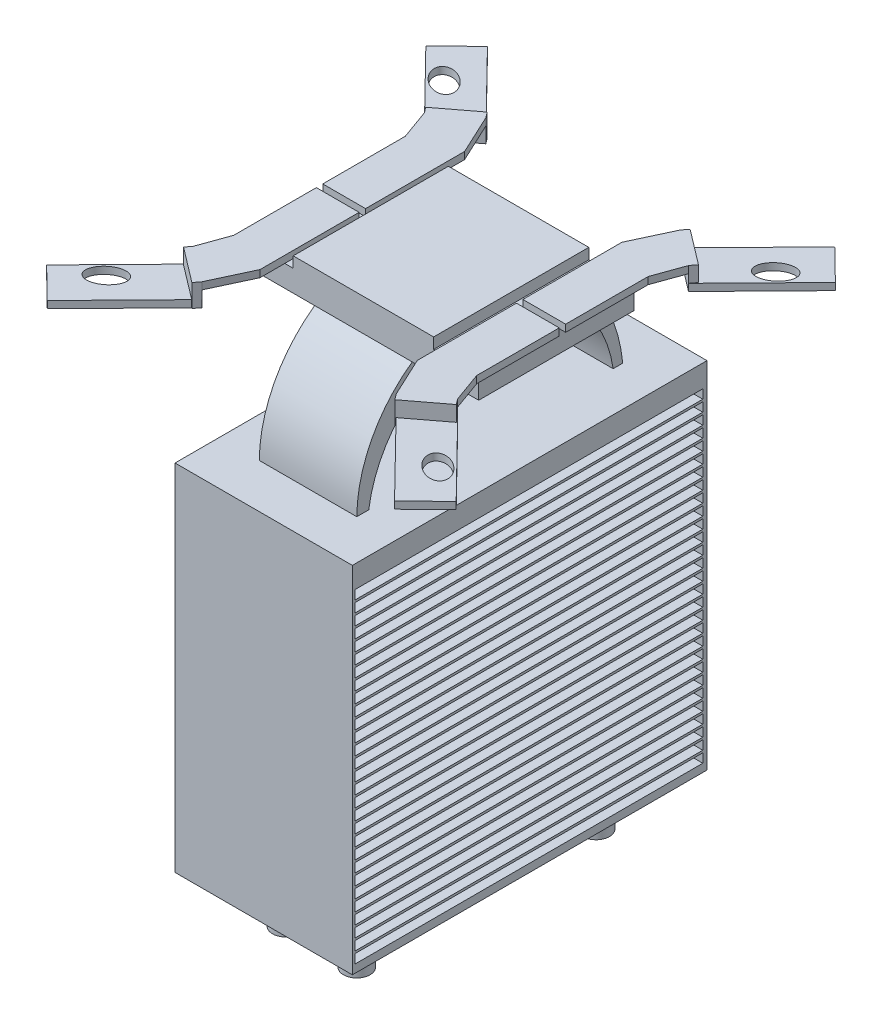
SolidWorks part; units mm, degrees
ref_plane "Front Plane" through (0, 0, 0) normal (0, 0, 1) x (1, 0, 0)
ref_plane "Top Plane" through (0, 0, 0) normal (0, 1, 0) x (1, 0, 0)
ref_plane "Right Plane" through (0, 0, 0) normal (1, 0, 0) x (0, 0, -1)
sketch "Sketch1" plane through (0, 0, 0) normal (0, 1, 0) x (1, 0, 0)
  line L1 (-52.1271, 39.0529) -> (-12.1271, 39.0529)
  line L2 (-52.1271, 39.0529) -> (-52.1271, -40.9471)
  line L3 (-52.1271, -40.9471) -> (-12.1271, -40.9471)
  line L4 (-12.1271, 39.0529) -> (-12.1271, -40.9471)
  dimension "D1" = 40
  dimension "D2" = 80
extrude "Boss-Extrude1" add sketch "Sketch1" along normal blind 80
sketch "Sketch2" plane through (0, 0, 0) normal (0, -1, 0) x (1, 0, 0)
  line L0 (-52.1271, -39.0529) -> (-52.1271, 40.9471) construction
  line L1 (-12.1271, 40.9471) -> (-12.1271, -39.0529) construction
  line L2 (-52.1271, 40.9471) -> (-12.1271, 40.9471) construction
  line L3 (-12.1271, -39.0529) -> (-52.1271, -39.0529) construction
  circle A0 centre (-40.1271, 27.9471) radius 3
  circle A1 centre (-40.1271, -26.0529) radius 3
  circle A2 centre (-24.1271, 27.9471) radius 3
  circle A3 centre (-24.1271, -26.0529) radius 3
  dimension "D1" = 12
  dimension "D2" = 12
  dimension "D3" = 13
  dimension "D4" = 13
  dimension "D5" = 13
  dimension "D6" = 13
  dimension "D7" = 12
  dimension "D8" = 12
extrude "Boss-Extrude2" add sketch "Sketch2" along normal blind 11
sketch "Sketch3" [suppressed] plane through (0, 80, 0) normal (0, 1, 0) x (1, 0, 0)
  line L0 (-12.1271, 39.0529) -> (-52.1271, 39.0529) construction
  line L1 (-52.1271, -40.9471) -> (-12.1271, -40.9471) construction
  line L2 (-52.1271, 39.0529) -> (-52.1271, -40.9471) construction
  line L3 (-12.1271, -40.9471) -> (-12.1271, 39.0529) construction
  circle A0 centre (-40.1271, 26.0529) radius 3
  circle A1 centre (-40.1271, -27.9471) radius 3
  circle A2 centre (-24.1271, 26.0529) radius 3
  circle A3 centre (-24.1271, -27.9471) radius 3
  dimension "D1" = 13
  dimension "D2" = 13
  dimension "D3" = 13
  dimension "D4" = 13
  dimension "D5" = 12
  dimension "D6" = 12
  dimension "D7" = 12
  dimension "D8" = 12
sketch "Sketch7" plane through (0, 80, 0) normal (0, 1, 0) x (1, 0, 0)
  line L1 (-43.1271, 29.0529) -> (-21.1271, 29.0529)
  line L2 (-43.1271, 29.0529) -> (-43.1271, -30.9471)
  line L3 (-43.1271, -30.9471) -> (-21.1271, -30.9471)
  line L4 (-21.1271, 29.0529) -> (-21.1271, -30.9471)
extrude "Boss-Extrude4" add sketch "Sketch7" along normal blind 24
sketch "Sketch8" plane through (0, 104, 0) normal (0, 1, 0) x (1, 0, 0)
  line L1 (-58.1271, 16.5529) -> (-6.1271, 16.5529)
  line L2 (-58.1271, 16.5529) -> (-58.1271, -18.4471)
  line L3 (-58.1271, -18.4471) -> (-6.1271, -18.4471)
  line L4 (-6.1271, 16.5529) -> (-6.1271, -18.4471)
  line L5 (-12.1271, 39.0529) -> (-52.1271, 39.0529) construction
  line L7 (-52.1271, 39.0529) -> (-52.1271, -40.9471) construction
  point P4 (-32.1271, 16.5529)
  point P8 (-58.1271, -0.9471)
  dimension "D1" = 52
  dimension "D2" = 35
  dimension "D3" = 40
  dimension "D4" = 20
extrude "Boss-Extrude5" add sketch "Sketch8" along normal blind 4.86
sketch "Sketch9" plane through (0, 108.86, 0) normal (0, 1, 0) x (1, 0, 0)
  line L0 (-6.1271, 16.5529) -> (-58.1271, 16.5529) construction
  line L1 (-47.9671, 16.5529) -> (-16.2871, 16.5529)
  line L2 (-47.9671, 16.5529) -> (-47.9671, -18.4471)
  line L3 (-47.9671, -18.4471) -> (-16.2871, -18.4471)
  line L4 (-16.2871, 16.5529) -> (-16.2871, -18.4471)
  line L5 (-58.1271, -18.4471) -> (-6.1271, -18.4471) construction
  line L6 (-58.1271, 16.5529) -> (-58.1271, -18.4471) construction
  line L7 (-6.1271, -18.4471) -> (-6.1271, 16.5529) construction
  dimension "D1" = 10.16
  dimension "D2" = 10.16
  dimension "D3" = 31.68
  dimension "D4" = 35
  dimension "D5" = 31.68
extrude "Boss-Extrude6" add sketch "Sketch9" along normal blind 2.4384
sketch "Sketch10" plane through (0, 108.86, 0) normal (0, 1, 0) x (1, 0, 0)
  line L0 (-16.2871, -18.4471) -> (-16.2871, 16.5529) construction
  line L1 (-14.3821, -1.6721) -> (-4.7301, -1.6721)
  line L2 (-14.3821, -1.6721) -> (-14.3821, -24.0241)
  line L3 (-47.9671, -0.9471) -> (-67.7333, -0.9471) construction
  line L4 (-4.7301, -1.6721) -> (-4.7301, -20.2903)
  line L5 (-14.3821, -24.0241) -> (-10.2049, -32.9783)
  line L6 (-10.2049, -32.9783) -> (-2.3202, -26.9816)
  line L7 (-4.7301, -20.2903) -> (-2.3202, -26.9816)
  line L8 (-16.2871, -0.9471) -> (3.4792, -0.9471) construction
  line L9 (-32.1271, -16.0781) -> (-32.1271, 19.2692) construction
  line L10 (-16.2871, 16.5529) -> (-47.9671, 16.5529) construction
  line L11 (-14.3821, -0.2221) -> (-4.7301, -0.2221)
  line L12 (-4.7301, -0.2221) -> (-4.7301, 18.3961)
  line L13 (-14.3821, -0.2221) -> (-14.3821, 22.1299)
  line L14 (-4.7301, 18.3961) -> (-2.3202, 25.0873)
  line L15 (-10.2049, 31.084) -> (-2.3202, 25.0873)
  line L17 (-14.3821, 22.1299) -> (-10.2049, 31.084)
  line L18 (-47.9671, 16.5529) -> (-47.9671, -18.4471) construction
  line L19 (-49.8721, 22.1299) -> (-54.0493, 31.084)
  line L21 (-54.0493, 31.084) -> (-61.9339, 25.0873)
  line L22 (-59.5241, 18.3961) -> (-61.9339, 25.0873)
  line L23 (-49.8721, -0.2221) -> (-49.8721, 22.1299)
  line L24 (-59.5241, -0.2221) -> (-59.5241, 18.3961)
  line L25 (-49.8721, -0.2221) -> (-59.5241, -0.2221)
  line L26 (-47.9671, -0.9471) -> (-67.7333, -0.9471) construction
  line L27 (-59.5241, -20.2903) -> (-61.9339, -26.9816)
  line L28 (-54.0493, -32.9783) -> (-61.9339, -26.9816)
  line L29 (-49.8721, -24.0241) -> (-54.0493, -32.9783)
  line L30 (-59.5241, -1.6721) -> (-59.5241, -20.2903)
  line L32 (-49.8721, -1.6721) -> (-49.8721, -24.0241)
  line L33 (-49.8721, -1.6721) -> (-59.5241, -1.6721)
  circle A0 centre (-9.2547, -4.8403) radius 2.3178
  dimension "D1" = 1.905
  dimension "D2" = 9.906
  dimension "D3" = 9.8806
  dimension "D4" = 7.112
  dimension "D5" = 0.725
  dimension "D6" = 15.84
  dimension "D7" = 18.6182
  dimension "D8" = 22.352
  dimension "D9" = 17.5
  dimension "D10" = 9.652
extrude "Boss-Extrude9" add sketch "Sketch10" along normal blind 1.6002 contours L30 L27 L28 L29 L32 L33 | L24 L22 L21 L19 L23 L25 | L13 L17 L15 L14 L12 L11 | L4 L7 L6 L5 L2 L1
sketch "Sketch13" plane through (12.1505, 0, 15.9759) normal (0.6054, 0, 0.796) x (0.796, 0, -0.6054)
  line L1 (-28.0864, 110.4602) -> (-18.1924, 110.4602)
  line L2 (-28.0864, 110.4602) -> (-28.0864, 105.3802)
  line L3 (-28.0864, 105.3802) -> (-18.1924, 105.3802)
  line L4 (-18.1924, 110.4602) -> (-18.1924, 105.3802)
  dimension "D1" = 5.08
extrude "Boss-Extrude10" add sketch "Sketch13" along normal blind 1.6002
sketch "Sketch12" plane through (-12.1271, 0, 0) normal (1, 0, 0) x (0, 0, -1)
  line L0 (-40.3776, 72.4257) -> (38.1108, 72.4257)
  line L1 (-40.3776, 74.9657) -> (38.1108, 74.9657)
  line L2 (-40.3776, 74.9657) -> (-40.3776, 72.9337)
  line L3 (-40.3776, 72.9337) -> (38.1108, 72.9337)
  line L4 (38.1108, 74.9657) -> (38.1108, 72.9337)
  line L5 (-40.3776, 72.4257) -> (-40.3776, 70.3937)
  line L6 (-40.3776, 70.3937) -> (38.1108, 70.3937)
  line L7 (38.1108, 72.4257) -> (38.1108, 70.3937)
  line L8 (-40.3776, 69.8857) -> (38.1108, 69.8857)
  line L9 (-40.3776, 69.8857) -> (-40.3776, 67.8537)
  line L10 (-40.3776, 67.8537) -> (38.1108, 67.8537)
  line L11 (38.1108, 69.8857) -> (38.1108, 67.8537)
  line L12 (-40.3776, 67.3457) -> (38.1108, 67.3457)
  line L13 (-40.3776, 67.3457) -> (-40.3776, 65.3137)
  line L14 (-40.3776, 65.3137) -> (38.1108, 65.3137)
  line L15 (38.1108, 67.3457) -> (38.1108, 65.3137)
  line L16 (-40.3776, 64.8057) -> (38.1108, 64.8057)
  line L17 (-40.3776, 64.8057) -> (-40.3776, 62.7737)
  line L18 (-40.3776, 62.7737) -> (38.1108, 62.7737)
  line L19 (38.1108, 64.8057) -> (38.1108, 62.7737)
  line L20 (-40.3776, 62.2657) -> (38.1108, 62.2657)
  line L21 (-40.3776, 62.2657) -> (-40.3776, 60.2337)
  line L22 (-40.3776, 60.2337) -> (38.1108, 60.2337)
  line L23 (38.1108, 62.2657) -> (38.1108, 60.2337)
  line L24 (-40.3776, 59.7257) -> (38.1108, 59.7257)
  line L25 (-40.3776, 59.7257) -> (-40.3776, 57.6937)
  line L26 (-40.3776, 57.6937) -> (38.1108, 57.6937)
  line L27 (38.1108, 59.7257) -> (38.1108, 57.6937)
  line L28 (-40.3776, 57.1857) -> (38.1108, 57.1857)
  line L29 (-40.3776, 57.1857) -> (-40.3776, 55.1537)
  line L30 (-40.3776, 55.1537) -> (38.1108, 55.1537)
  line L31 (38.1108, 57.1857) -> (38.1108, 55.1537)
  line L32 (-40.3776, 54.6457) -> (38.1108, 54.6457)
  line L33 (-40.3776, 54.6457) -> (-40.3776, 52.6137)
  line L34 (-40.3776, 52.6137) -> (38.1108, 52.6137)
  line L35 (38.1108, 54.6457) -> (38.1108, 52.6137)
  line L36 (-40.3776, 52.1057) -> (38.1108, 52.1057)
  line L37 (-40.3776, 52.1057) -> (-40.3776, 50.0737)
  line L38 (-40.3776, 50.0737) -> (38.1108, 50.0737)
  line L39 (38.1108, 52.1057) -> (38.1108, 50.0737)
  line L40 (-40.3776, 49.5657) -> (38.1108, 49.5657)
  line L41 (-40.3776, 49.5657) -> (-40.3776, 47.5337)
  line L42 (-40.3776, 47.5337) -> (38.1108, 47.5337)
  line L43 (38.1108, 49.5657) -> (38.1108, 47.5337)
  line L44 (-40.3776, 47.0257) -> (38.1108, 47.0257)
  line L45 (-40.3776, 47.0257) -> (-40.3776, 44.9937)
  line L46 (-40.3776, 44.9937) -> (38.1108, 44.9937)
  line L47 (38.1108, 47.0257) -> (38.1108, 44.9937)
  line L48 (-40.3776, 44.4857) -> (38.1108, 44.4857)
  line L49 (-40.3776, 44.4857) -> (-40.3776, 42.4537)
  line L50 (-40.3776, 42.4537) -> (38.1108, 42.4537)
  line L51 (38.1108, 44.4857) -> (38.1108, 42.4537)
  line L52 (-40.3776, 41.9457) -> (38.1108, 41.9457)
  line L53 (-40.3776, 41.9457) -> (-40.3776, 39.9137)
  line L54 (-40.3776, 39.9137) -> (38.1108, 39.9137)
  line L55 (38.1108, 41.9457) -> (38.1108, 39.9137)
  line L56 (-40.3776, 39.4057) -> (38.1108, 39.4057)
  line L57 (-40.3776, 39.4057) -> (-40.3776, 37.3737)
  line L58 (-40.3776, 37.3737) -> (38.1108, 37.3737)
  line L59 (38.1108, 39.4057) -> (38.1108, 37.3737)
  line L60 (-40.3776, 36.8657) -> (38.1108, 36.8657)
  line L61 (-40.3776, 36.8657) -> (-40.3776, 34.8337)
  line L62 (-40.3776, 34.8337) -> (38.1108, 34.8337)
  line L63 (38.1108, 36.8657) -> (38.1108, 34.8337)
  line L64 (-40.3776, 34.3257) -> (38.1108, 34.3257)
  line L65 (-40.3776, 34.3257) -> (-40.3776, 32.2937)
  line L66 (-40.3776, 32.2937) -> (38.1108, 32.2937)
  line L67 (38.1108, 34.3257) -> (38.1108, 32.2937)
  line L68 (-40.3776, 31.7857) -> (38.1108, 31.7857)
  line L69 (-40.3776, 31.7857) -> (-40.3776, 29.7537)
  line L70 (-40.3776, 29.7537) -> (38.1108, 29.7537)
  line L71 (38.1108, 31.7857) -> (38.1108, 29.7537)
  line L72 (-40.3776, 29.2457) -> (38.1108, 29.2457)
  line L73 (-40.3776, 29.2457) -> (-40.3776, 27.2137)
  line L74 (-40.3776, 27.2137) -> (38.1108, 27.2137)
  line L75 (38.1108, 29.2457) -> (38.1108, 27.2137)
  line L76 (-40.3776, 26.7057) -> (38.1108, 26.7057)
  line L77 (-40.3776, 26.7057) -> (-40.3776, 24.6737)
  line L78 (-40.3776, 24.6737) -> (38.1108, 24.6737)
  line L79 (38.1108, 26.7057) -> (38.1108, 24.6737)
  line L80 (-40.3776, 24.1657) -> (38.1108, 24.1657)
  line L81 (-40.3776, 24.1657) -> (-40.3776, 22.1337)
  line L82 (-40.3776, 22.1337) -> (38.1108, 22.1337)
  line L83 (38.1108, 24.1657) -> (38.1108, 22.1337)
  line L84 (-40.3776, 21.6257) -> (38.1108, 21.6257)
  line L85 (-40.3776, 21.6257) -> (-40.3776, 19.5937)
  line L86 (-40.3776, 19.5937) -> (38.1108, 19.5937)
  line L87 (38.1108, 21.6257) -> (38.1108, 19.5937)
  line L88 (-40.3776, 19.0857) -> (38.1108, 19.0857)
  line L89 (-40.3776, 19.0857) -> (-40.3776, 17.0537)
  line L90 (-40.3776, 17.0537) -> (38.1108, 17.0537)
  line L91 (38.1108, 19.0857) -> (38.1108, 17.0537)
  line L92 (-40.3776, 16.5457) -> (38.1108, 16.5457)
  line L93 (-40.3776, 16.5457) -> (-40.3776, 14.5137)
  line L94 (-40.3776, 14.5137) -> (38.1108, 14.5137)
  line L95 (38.1108, 16.5457) -> (38.1108, 14.5137)
  line L96 (-40.3776, 14.0057) -> (38.1108, 14.0057)
  line L97 (-40.3776, 14.0057) -> (-40.3776, 11.9737)
  line L98 (-40.3776, 11.9737) -> (38.1108, 11.9737)
  line L99 (38.1108, 14.0057) -> (38.1108, 11.9737)
  line L100 (-40.3776, 11.4657) -> (38.1108, 11.4657)
  line L101 (-40.3776, 11.4657) -> (-40.3776, 9.4337)
  line L102 (-40.3776, 9.4337) -> (38.1108, 9.4337)
  line L103 (38.1108, 11.4657) -> (38.1108, 9.4337)
  line L104 (-40.3776, 8.9257) -> (38.1108, 8.9257)
  line L105 (-40.3776, 8.9257) -> (-40.3776, 6.8937)
  line L106 (-40.3776, 6.8937) -> (38.1108, 6.8937)
  line L107 (38.1108, 8.9257) -> (38.1108, 6.8937)
  line L108 (-40.3776, 6.3857) -> (38.1108, 6.3857)
  line L109 (-40.3776, 6.3857) -> (-40.3776, 4.3537)
  line L110 (-40.3776, 4.3537) -> (38.1108, 4.3537)
  line L111 (38.1108, 6.3857) -> (38.1108, 4.3537)
  line L112 (-40.3776, 3.8457) -> (38.1108, 3.8457)
  line L113 (-40.3776, 3.8457) -> (-40.3776, 1.8137)
  line L114 (-40.3776, 1.8137) -> (38.1108, 1.8137)
  line L115 (38.1108, 3.8457) -> (38.1108, 1.8137)
  dimension "D1" = 2.032
  dimension "D2" = 29
extrude "Cut-Extrude1" cut sketch "Sketch12" against normal through all
sketch "Sketch15" plane through (0, 105.3802, 0) normal (0, -1, 0) x (1, 0, 0)
  line L0 (7.0448, 50.599) -> (14.0673, 43.722)
  line L1 (-10.2049, 32.9783) -> (-2.3297, 26.9889) construction
  line L3 (-10.2084, 32.981) -> (7.0448, 50.599)
  line L4 (-2.3237, 26.9843) -> (14.0673, 43.722)
  line L5 (-2.3237, 26.9843) -> (-10.2084, 32.981)
  ellipse E0 centre (5.2709, 39.0498) end of major axis (2.1824, 36.6748) minor radius 2.54
  dimension "D1" = 5.08
  dimension "D2" = 24.659
  dimension "D3" = 9.8291
  dimension "D4" = 23.4268
  dimension "D5" = 9.906
  dimension "D6" = 6.8133
  dimension "D7" = 9.4926
extrude "Boss-Extrude11" add sketch "Sketch15" against normal blind 1.6002
sketch "Sketch11" [suppressed] plane through (0, 108.86, 0) normal (0, -1, 0) x (1, 0, 0)
  line L0 (-61.9339, -25.0873) -> (-78.3249, -41.825)
  line L1 (-54.0493, -31.084) -> (-71.3024, -48.7021)
  line L2 (-71.3024, -48.7021) -> (-78.3249, -41.825)
  line L3 (-61.9339, 26.9816) -> (-78.3249, 43.7193)
  line L4 (-54.0493, 32.9783) -> (-71.3024, 50.5964)
  line L5 (-16.2871, 18.4471) -> (-16.2871, -16.5529) construction
  line L6 (-32.1271, -13.8858) -> (-32.1271, 30.975) construction
  line L7 (-16.2871, 0.9471) -> (-1.354, 0.9471) construction
  line L8 (-47.9671, 0.9471) -> (-62.9001, 0.9471) construction
  line L9 (-47.9671, -16.5529) -> (-47.9671, 18.4471) construction
  line L10 (-71.3024, 50.5964) -> (-78.3249, 43.7193)
  line L13 (-16.2871, 0.9471) -> (-1.354, 0.9471) construction
  line L14 (7.0483, 50.5964) -> (14.0708, 43.7193)
  line L15 (-10.2049, 32.9783) -> (7.0483, 50.5964)
  line L16 (-2.3202, 26.9816) -> (14.0708, 43.7193)
  line L17 (7.0483, -48.7021) -> (14.0708, -41.825)
  line L18 (-10.2049, -31.084) -> (7.0483, -48.7021)
  line L19 (-2.3202, -25.0873) -> (14.0708, -41.825)
  line L20 (-61.9339, -25.0873) -> (-54.0493, -31.084)
  line L21 (-61.9339, 26.9816) -> (-54.0493, 32.9783)
  line L22 (-2.3202, 26.9816) -> (-10.2049, 32.9783)
  line L23 (-2.3202, -25.0873) -> (-10.2049, -31.084)
  ellipse E0 centre (-69.5286, -37.1529) end of major axis (-66.8533, -35.0956) minor radius 2.2001
  ellipse E1 centre (-69.5286, 39.0471) end of major axis (-72.2038, 41.1044) minor radius 2.2001
  ellipse E2 centre (5.2744, 39.0471) end of major axis (7.9497, 41.1044) minor radius 2.2001
  ellipse E3 centre (5.2744, -37.1529) end of major axis (7.9497, -39.2101) minor radius 2.2001
  dimension "D1" = 15.84
  dimension "D2" = 76.2
  dimension "D3" = 74.803
  dimension "D4" = 4.4002
ref_axis "Axis5" [suppressed] through (-62.9001, 108.86, 0.9471) along (1, 0, 0)
ref_axis "Axis6" [suppressed] through (-32.1271, 108.86, -13.8858) along (0, 0, 1)
ref_plane "Plane1" [suppressed] through (0, 0, 0.9471) normal (0, 0, 1) x (1, 0, 0)
mirror "Mirror1" about plane through (0, 0, 0.9471) normal (0, 0, 1) of "Boss-Extrude11", "Boss-Extrude10"
ref_plane "Plane2" [suppressed] through (-32.1271, 0, 0) normal (1, 0, 0) x (0, 0, -1)
mirror "Mirror2" about plane through (-32.1271, 0, 0) normal (1, 0, 0) of "Mirror1"
ref_point "Point3" [suppressed]
ref_point "Point4" [suppressed]
ref_point "Point5" [suppressed]
ref_point "Point6"
sketch "Sketch22" plane through (-21.1271, 0, 0) normal (1, 0, 0) x (0, 0, -1)
  line L0 (-40.9471, 80) -> (39.0529, 80) construction
  line L1 (-30.9471, 80) -> (29.0529, 80) construction
  line L2 (-28.2454, 80) -> (26.8863, 80)
  arc A0 (-28.2454, 80) -> (26.8863, 80) centre (-0.6796, 76.0291) cw
extrude "Cut-Extrude15" cut sketch "Sketch22" against normal blind 25.4
sketch "Sketch24" plane through (-21.1271, 0, 0) normal (1, 0, 0) x (0, 0, -1)
  line L0 (-30.9471, 104) -> (-18.4471, 104)
  line L1 (-30.9471, 104) -> (-30.9471, 80)
  arc A0 (-30.9471, 80) -> (-18.4471, 104) centre (-1.1084, 79.7142) cw
extrude "Cut-Extrude16" cut sketch "Sketch24" against normal blind 25.4
sketch "Sketch25" plane through (-21.1271, 0, 0) normal (1, 0, 0) x (0, 0, -1)
  line L0 (16.5529, 104) -> (29.0529, 104)
  line L1 (29.0529, 104) -> (29.0529, 80)
  arc A0 (29.0529, 80) -> (16.5529, 104) centre (-7.0405, 76.4566) ccw
extrude "Cut-Extrude17" cut sketch "Sketch25" against normal blind 25.4
equation "\"D3@Sketch8\" = \"D2@Sketch1\"/2"
equation "\"D4@Sketch8\" = \"D1@Sketch1\"/2"
equation "\"D6@Sketch10\" = \"D3@Sketch9\"/2"
equation "\"D9@Sketch10\" =\"D4@Sketch9\"/2"
equation "\"D1@Sketch11\" = \"D3@Sketch9\"/2"
